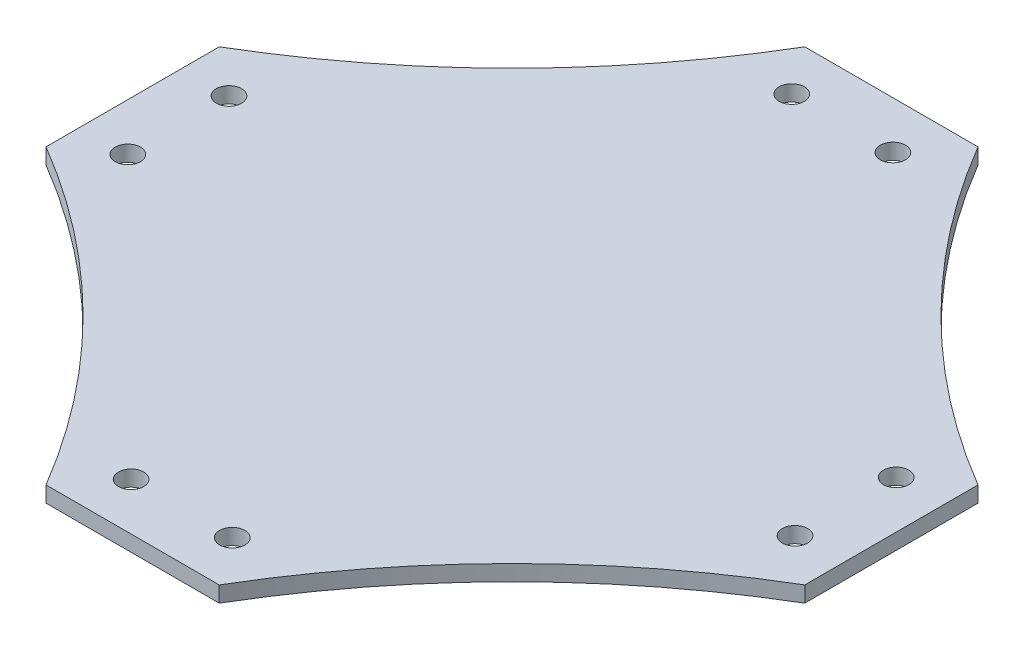
SolidWorks part; units mm, degrees
material "PBTP"
ref_plane "Front Plane" through (0, 0, 0) normal (0, 0, 1) x (1, 0, 0)
ref_plane "Top Plane" through (0, 0, 0) normal (0, 1, 0) x (1, 0, 0)
ref_plane "Right Plane" through (0, 0, 0) normal (1, 0, 0) x (0, 0, -1)
sketch "Sketch1" plane through (0, 0, 0) normal (0, 1, 0) x (1, 0, 0)
  line L0 (0, 0) -> (0, 60) construction
  line L1 (-13.7, 60) -> (13.7, 60)
  line L2 (60, 13.7) -> (60, -13.7)
  line L3 (13.7, -60) -> (-13.7, -60)
  line L4 (-60, -13.7) -> (-60, 13.7)
  line L5 (0, 0) -> (-75.007, 75.007) construction
  circle A0 centre (0, 0) radius 13.4565 construction
  arc A1 (-13.7, 60) -> (-60, 13.7) centre (-126.7477, 126.7477) cw
  arc A2 (60, 13.7) -> (13.7, 60) centre (126.7477, 126.7477) cw
  arc A3 (13.7, -60) -> (60, -13.7) centre (126.7477, -126.7477) cw
  arc A4 (-60, -13.7) -> (-13.7, -60) centre (-126.7477, -126.7477) cw
  point P8 (0, 60)
  point P17 (0, 0)
  point P28 (0, 0)
  point P29 (0, 0)
  point P30 (0, 0)
  dimension "D6" = 4
  dimension "D1" = 27.4
  dimension "D2" = 60
  dimension "D4" = 45
  dimension "D3" = 4
  dimension "D5" = 120
extrude "Boss-Extrude1" add sketch "Sketch1" along normal blind 2.5
sketch "Sketch2" plane through (0, 2.5, 0) normal (0, 1, 0) x (1, 0, 0)
  line L0 (0, 60) -> (0, -60) construction
  line L1 (13.7, 60) -> (-13.7, 60) construction
  line L2 (-13.7, -60) -> (13.7, -60) construction
sketch "Sketch3" plane through (0, 2.5, 0) normal (0, 1, 0) x (1, 0, 0)
  line L0 (13.7, 60) -> (-13.7, 60) construction
  circle A0 centre (-8.2597, 52.5) radius 2
  circle A1 centre (7.7403, 52.5) radius 2
  dimension "D1" = 4
  dimension "D2" = 4
  dimension "D3" = 16
  dimension "D4" = 7.5
extrude "Cut-Extrude1" cut sketch "Sketch3" against normal blind 2.5
ref_axis "Axis1" through (0, 0, 0) along (0, 1, 0)
pattern_circular "CirPattern1" count 4 over 360 about axis through (0, 0, 0) along (0, 1, 0) of "Cut-Extrude1"
